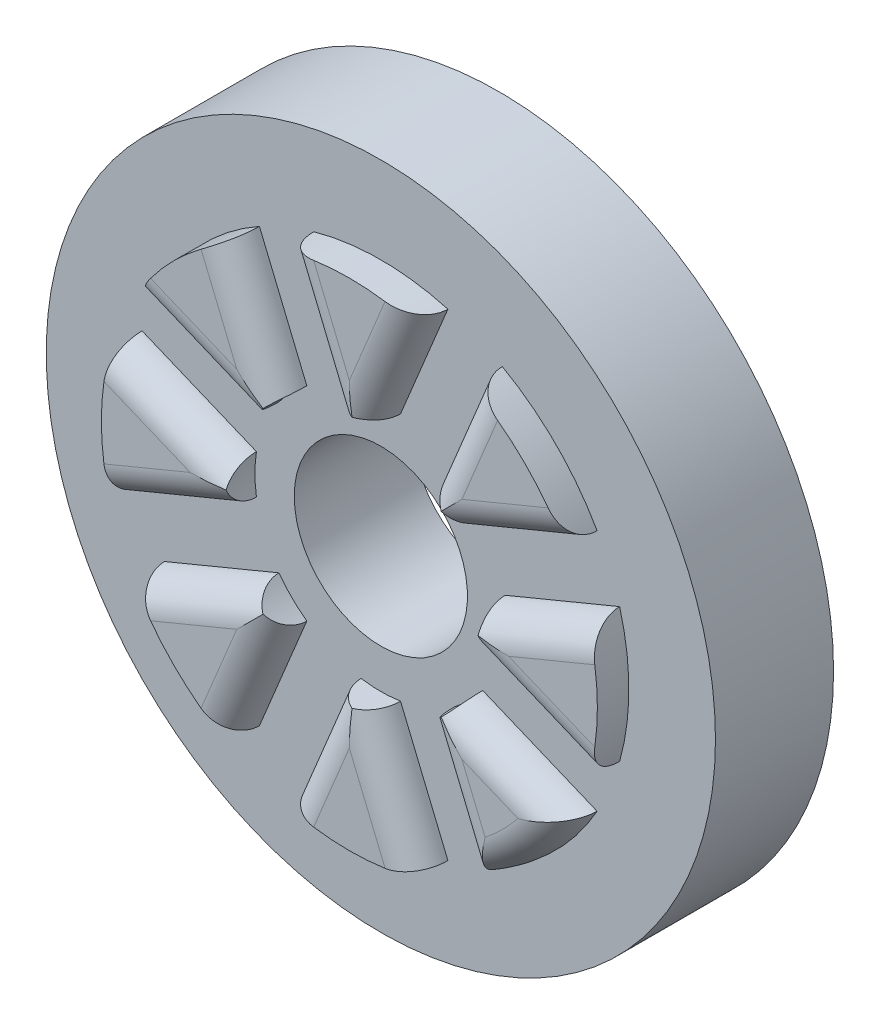
SolidWorks part; units mm, degrees
ref_plane "Front Plane" through (0, 0, 0) normal (0, 0, 1) x (1, 0, 0)
ref_plane "Top Plane" through (0, 0, 0) normal (0, 1, 0) x (1, 0, 0)
ref_plane "Right Plane" through (0, 0, 0) normal (1, 0, 0) x (0, 0, -1)
sketch "Sketch1" plane through (0, 0, 0) normal (0, 0, 1) x (1, 0, 0)
  circle A0 centre (0, 0) radius 8.5
  dimension "D1" = 17
extrude "Boss-Extrude1" add sketch "Sketch1" along normal blind 3
sketch "Sketch2" plane through (0, 0, 0) normal (0, 0, -1) x (-1, 0, 0)
  line L0 (-4.0105, 1.4727) -> (-3.2807, -2.7369)
  line L1 (-5.0945, 1.8707) -> (-4.1673, -3.4766)
  line L2 (-4.1673, -3.4766) -> (0.9271, -5.3473)
  line L3 (0.9271, -5.3473) -> (5.0945, -1.8707)
  line L4 (5.0945, -1.8707) -> (4.1673, 3.4766)
  line L5 (4.1673, 3.4766) -> (-0.9271, 5.3473)
  line L6 (-0.9271, 5.3473) -> (-5.0945, 1.8707)
  line L7 (-3.2807, -2.7369) -> (0.7299, -4.2096)
  line L8 (0.7299, -4.2096) -> (4.0105, -1.4727)
  line L9 (4.0105, -1.4727) -> (3.2807, 2.7369)
  line L10 (3.2807, 2.7369) -> (-0.7299, 4.2096)
  line L11 (-0.7299, 4.2096) -> (-4.0105, 1.4727)
  circle A0 centre (0, 0) radius 4.7 construction
  circle A1 centre (0, 0) radius 3.7
  dimension "D1" = 9.4
  dimension "D2" = 1
extrude "Boss-Extrude2" add sketch "Sketch2" along normal blind 8 contours L5 L6 L1 L2 L3 L4 L11 L10 L9 L8 L7 L0 region at (2.9162, 3.4956, 0)
sketch "Sketch3" plane through (0, 0, 3) normal (0, 0, 1) x (1, 0, 0)
  line L0 (-8.5, 0) -> (8.5, 0) construction
  line L1 (-3.1607, 0.5) -> (-6.0654, 1.7032)
  line L2 (-6.1607, -0.5) -> (-3.1607, -0.5) construction
  line L3 (-6.1607, -0.5) -> (-6.1607, 0.5) construction
  line L4 (-6.1607, 0.5) -> (-3.1607, 0.5) construction
  line L6 (-6.1607, -0.5) -> (-3.1607, 0.5) construction
  line L7 (-6.1607, 0.5) -> (-3.1607, -0.5) construction
  line L8 (-3.1607, -0.5) -> (-6.0654, -1.7032)
  line L9 (-1.8814, 2.5885) -> (-3.0846, 5.4932)
  line L10 (-2.5885, 1.8814) -> (-5.4932, 3.0846)
  line L11 (0.5, 3.1607) -> (1.7032, 6.0654)
  line L12 (-0.5, 3.1607) -> (-1.7032, 6.0654)
  line L13 (2.5885, 1.8814) -> (5.4932, 3.0846)
  line L14 (1.8814, 2.5885) -> (3.0846, 5.4932)
  line L15 (3.1607, -0.5) -> (6.0654, -1.7032)
  line L16 (3.1607, 0.5) -> (6.0654, 1.7032)
  line L17 (1.8814, -2.5885) -> (3.0846, -5.4932)
  line L18 (2.5885, -1.8814) -> (5.4932, -3.0846)
  line L19 (-0.5, -3.1607) -> (-1.7032, -6.0654)
  line L20 (0.5, -3.1607) -> (1.7032, -6.0654)
  line L21 (-2.5885, -1.8814) -> (-5.4932, -3.0846)
  line L22 (-1.8814, -2.5885) -> (-3.0846, -5.4932)
  circle A0 centre (0, 0) radius 8.5 construction
  arc A3 (-2.5885, -1.8814) -> (-1.8814, -2.5885) centre (0, 0) ccw
  arc A4 (-5.4932, -3.0846) -> (-3.0846, -5.4932) centre (0, 0) ccw
  arc A5 (-1.7032, -6.0654) -> (1.7032, -6.0654) centre (0, 0) ccw
  arc A6 (-0.5, -3.1607) -> (0.5, -3.1607) centre (0, 0) ccw
  arc A7 (1.8814, -2.5885) -> (2.5885, -1.8814) centre (0, 0) ccw
  arc A8 (3.0846, -5.4932) -> (5.4932, -3.0846) centre (0, 0) ccw
  arc A9 (3.1607, -0.5) -> (3.1607, 0.5) centre (0, 0) ccw
  arc A10 (6.0654, -1.7032) -> (6.0654, 1.7032) centre (0, 0) ccw
  arc A11 (2.5885, 1.8814) -> (1.8814, 2.5885) centre (0, 0) ccw
  arc A12 (5.4932, 3.0846) -> (3.0846, 5.4932) centre (0, 0) ccw
  arc A13 (1.7032, 6.0654) -> (-1.7032, 6.0654) centre (0, 0) ccw
  arc A14 (-1.8814, 2.5885) -> (-2.5885, 1.8814) centre (0, 0) ccw
  arc A15 (-3.0846, 5.4932) -> (-5.4932, 3.0846) centre (0, 0) ccw
  arc A16 (0.5, 3.1607) -> (-0.5, 3.1607) centre (0, 0) ccw
  arc A17 (-6.0654, 1.7032) -> (-6.0654, -1.7032) centre (0, 0) ccw
  arc A18 (-3.1607, 0.5) -> (-3.1607, -0.5) centre (0, 0) ccw
  point P5 (-4.6607, 0)
  point P50 (0, 0)
  dimension "D3" = 6.3
  dimension "D5" = 3.2
  dimension "D1" = 1
  dimension "D2" = 3
  dimension "D4" = 8
extrude "Boss-Extrude4" add sketch "Sketch3" along normal blind 0.8
fillet "Fillet3" radius 0.8 17 edges at (4.0409, -2.483, 3.8) (4.4548, -4.4548, 3.8) (2.483, -4.0409, 3.8) (4.0409, 2.483, 3.8) (2.483, 4.0409, 3.8) (1.1016, 4.6131, 3.8) (-1.1016, 4.6131, 3.8) (-2.483, 4.0409, 3.8) (-4.0409, 2.483, 3.8) (-4.6131, 1.1016, 3.8) (-4.6131, -1.1016, 3.8) (-2.483, -4.0409, 3.8) (-4.0409, -2.483, 3.8) (-1.1016, -4.6131, 3.8) (1.1016, -4.6131, 3.8) (4.6131, -1.1016, 3.8) (4.6131, 1.1016, 3.8)
sketch "Sketch4" plane through (0, 0, 0) normal (0, 0, -1) x (-1, 0, 0)
  circle A0 centre (0, 0) radius 2.2
  dimension "D1" = 4.4
extrude "Cut-Extrude1" cut sketch "Sketch4" against normal through all both and the other way through all
sketch "Sketch5" plane through (0, 0, -8) normal (0, 0, -1) x (-1, 0, 0)
  line L6 (4.1673, 3.4766) -> (-0.9271, 5.3473)
  line L7 (-0.9271, 5.3473) -> (-5.0945, 1.8707)
  line L8 (-5.0945, 1.8707) -> (-4.1673, -3.4766)
  line L9 (-4.1673, -3.4766) -> (0.9271, -5.3473)
  line L10 (0.9271, -5.3473) -> (5.0945, -1.8707)
  line L11 (5.0945, -1.8707) -> (4.1673, 3.4766)
  line L12 (4.1673, 3.4766) -> (-0.9271, 5.3473)
  line L13 (-0.9271, 5.3473) -> (-5.0945, 1.8707)
  line L14 (-5.0945, 1.8707) -> (-4.1673, -3.4766)
  line L15 (-4.1673, -3.4766) -> (0.9271, -5.3473)
  line L16 (0.9271, -5.3473) -> (5.0945, -1.8707)
  line L17 (5.0945, -1.8707) -> (4.1673, 3.4766)
  dimension "D1" = 0
extrude "Cut-Extrude2" cut sketch "Sketch5" against normal up to vertex (8 mm away) up to point (0.9271, 5.3473, 0)
